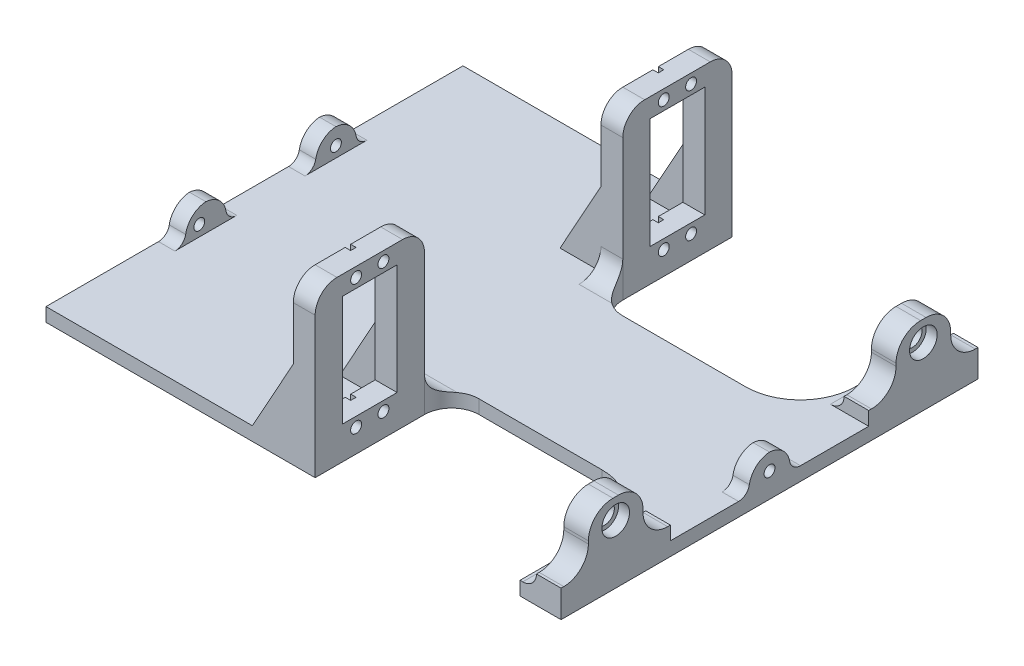
SolidWorks part; units mm, degrees
ref_plane "Front Plane" through (0, 0, 0) normal (0, 0, 1) x (1, 0, 0)
ref_plane "Top Plane" through (0, 0, 0) normal (0, 1, 0) x (1, 0, 0)
ref_plane "Right Plane" through (0, 0, 0) normal (1, 0, 0) x (0, 0, -1)
sketch "Sketch1" plane through (0, 0, 0) normal (0, 1, 0) x (1, 0, 0)
  line L1 (-183.5, 76.3) -> (183.5, 76.3)
  line L2 (-183.5, 76.3) -> (-183.5, -76.3)
  line L3 (-183.5, -76.3) -> (183.5, -76.3)
  line L4 (183.5, 76.3) -> (183.5, -76.3)
  line L5 (-183.5, 76.3) -> (183.5, -76.3) construction
  line L6 (-183.5, -76.3) -> (183.5, 76.3) construction
  point P0 (0, 0)
  dimension "D1" = 367
  dimension "D2" = 152.6
extrude "Boss-Extrude1" add sketch "Sketch1" along normal blind 5
sketch "Sketch2" plane through (0, 5, 0) normal (0, 1, 0) x (1, 0, 0)
  line L0 (173.5, -76.3) -> (173.5, -26.3)
  line L1 (-183.5, -76.3) -> (183.5, -76.3) construction
  line L2 (173.5, -26.3) -> (98.5, -26.3)
  line L3 (98.5, -26.3) -> (98.5, -76.3)
  line L4 (98.5, -76.3) -> (173.5, -76.3)
  line L5 (183.5, -76.3) -> (183.5, 76.3) construction
  dimension "D1" = 10
  dimension "D2" = 75
  dimension "D3" = 50
extrude "Cut-Extrude1" cut sketch "Sketch2" against normal through all
sketch "Sketch3" plane through (0, 5, 0) normal (0, 1, 0) x (1, 0, 0)
  line L0 (98.5, -36.3) -> (90.5, -36.3)
  line L1 (98.5, -26.3) -> (98.5, -76.3) construction
  line L2 (90.5, -36.3) -> (90.5, -76.3)
  line L3 (-183.5, -76.3) -> (98.5, -76.3) construction
  line L4 (90.5, -76.3) -> (98.5, -76.3)
  line L5 (98.5, -36.3) -> (98.5, -76.3)
  dimension "D1" = 8
  dimension "D2" = 40
extrude "Boss-Extrude2" add sketch "Sketch3" along normal blind 54.5
sketch "Sketch4" plane through (98.5, 0, 0) normal (1, 0, 0) x (0, 0, -1)
  line L0 (-76.3, 0) -> (-76.3, 59.5) construction
  line L1 (-66.3, 52.5) -> (-46.3, 52.5)
  line L2 (-66.3, 52.5) -> (-66.3, 12)
  line L3 (-66.3, 12) -> (-46.3, 12)
  line L4 (-46.3, 52.5) -> (-46.3, 12)
  line L5 (-66.3, 52.5) -> (-46.3, 12) construction
  line L6 (-66.3, 12) -> (-46.3, 52.5) construction
  line L12 (-76.3, 5) -> (76.3, 5) construction
  point P0 (-56.3, 32.25)
  dimension "D1" = 20
  dimension "D2" = 7
  dimension "D3" = 40.5
  dimension "D4" = 20
extrude "Cut-Extrude2" cut sketch "Sketch4" against normal blind 15
sketch "Sketch7" plane through (90.5, 0, 0) normal (-1, 0, 0) x (0, 0, 1)
  line L0 (46.3, 52.5) -> (66.3, 52.5) construction
  line L1 (55.3, 52.5) -> (57.3, 52.5)
  line L2 (55.3, 52.5) -> (55.3, 59.5)
  line L3 (55.3, 59.5) -> (57.3, 59.5)
  line L4 (57.3, 52.5) -> (57.3, 59.5)
  line L5 (55.3, 52.5) -> (57.3, 59.5) construction
  line L6 (55.3, 59.5) -> (57.3, 52.5) construction
  line L7 (36.3, 59.5) -> (76.3, 59.5) construction
  line L13 (-76.3, 5) -> (76.3, 5) construction
  line L14 (55.3, 12) -> (57.3, 12)
  line L17 (76.3, 59.5) -> (76.3, 5) construction
  line L18 (55.3, 12) -> (55.3, 5)
  line L19 (55.3, 5) -> (57.3, 5)
  line L20 (57.3, 12) -> (57.3, 5)
  line L21 (55.3, 12) -> (57.3, 5) construction
  line L22 (55.3, 5) -> (57.3, 12) construction
  point P4 (56.3, 56)
  point P9 (56.3, 8.5)
  point P13 (56.3, 8.5)
  dimension "D1" = 20
  dimension "D2" = 2
  dimension "D3" = 7
  dimension "D4" = 2
  dimension "D5" = 20
extrude "Cut-Extrude4" cut sketch "Sketch7" against normal blind 2
sketch "Sketch8" plane through (98.5, 0, 0) normal (1, 0, 0) x (0, 0, -1)
  line L0 (-46.3, 52.5) -> (-66.3, 52.5) construction
  line L1 (-76.3, 59.5) -> (-36.3, 59.5) construction
  line L2 (-66.3, 32.25) -> (-46.3, 32.25) construction
  line L3 (-66.3, 52.5) -> (-66.3, 12) construction
  line L4 (-46.3, 12) -> (-46.3, 52.5) construction
  circle A0 centre (-61.3, 56) radius 2
  circle A1 centre (-51.3, 56) radius 2
  circle A2 centre (-61.3, 8.5) radius 2
  circle A3 centre (-51.3, 8.5) radius 2
  point P6 (-56.3, 52.5)
  dimension "D1" = 4
  dimension "D2" = 4
  dimension "D3" = 5
  dimension "D4" = 5
  dimension "D5" = 3.5
  dimension "D6" = 3.5
extrude "Cut-Extrude5" cut sketch "Sketch8" against normal blind 15
fillet "Fillet1" radius 20 1 edges at (173.5, 2.5, 26.3)
fillet "Fillet3" radius 10 1 edges at (98.5, 2.5, 26.3)
fillet "Fillet9" radius 8 3 edges at (94.5, 5, 36.3) (94.5, 59.5, 36.3) (94.5, 59.5, 76.3)
sketch "Sketch13" plane through (0, 5, 0) normal (0, 1, 0) x (1, 0, 0)
  line L0 (183.5, 0) -> (-183.5, 0) construction
  line L1 (183.5, -76.3) -> (183.5, 76.3) construction
  line L2 (-183.5, 76.3) -> (-183.5, -76.3) construction
sketch "Sketch17" plane through (0, 5, 0) normal (0, 1, 0) x (1, 0, 0)
  line L0 (-183.5, -76.3) -> (90.5, -76.3) construction
  line L1 (-183.5, 76.3) -> (0, 76.3)
  line L2 (-183.5, 76.3) -> (-183.5, -76.3)
  line L3 (-183.5, -76.3) -> (0, -76.3)
  line L4 (0, 76.3) -> (0, -76.3)
  line L5 (-183.5, 76.3) -> (0, -76.3) construction
  line L6 (-183.5, -76.3) -> (0, 76.3) construction
  point P4 (-91.75, 0)
extrude "Cut-Extrude8" cut sketch "Sketch17" against normal through all both and the other way through all
sketch "Sketch18" plane through (0, 5, 0) normal (0, 1, 0) x (1, 0, 0)
  line L0 (20, 51.3) -> (20, -98.7)
  line L1 (20, -98.7) -> (100, -98.7)
  line L2 (100, -98.7) -> (100, -30)
  line L3 (100, -30) -> (163.5, -30)
  line L4 (163.5, -30) -> (163.5, 30)
  line L5 (163.5, 30) -> (100, 30)
  line L6 (100, 30) -> (100, 51.3)
  line L7 (100, 51.3) -> (20, 51.3)
  line L8 (183.5, 0) -> (-183.5, 0) construction
  line L9 (183.5, 76.3) -> (0, 76.3) construction
  line L10 (183.5, -76.3) -> (183.5, 76.3) construction
  line L11 (0, -76.3) -> (0, 76.3) construction
  dimension "D1" = 150
  dimension "D2" = 25
  dimension "D3" = 30
  dimension "D4" = 30
  dimension "D5" = 20
  dimension "D6" = 20
  dimension "D7" = 80
  dimension "D8" = 80
sketch "Sketch19" plane through (0, 5, 0) normal (0, 1, 0) x (1, 0, 0)
  line L1 (0, 31.3) -> (6, 31.3)
  line L2 (0, 31.3) -> (0, 16.3)
  line L3 (0, 16.3) -> (6, 16.3)
  line L4 (6, 31.3) -> (6, 16.3)
  line L5 (0, 31.3) -> (6, 16.3) construction
  line L6 (0, 16.3) -> (6, 31.3) construction
  line L9 (0, -31.3) -> (6, -31.3)
  line L10 (6, -16.3) -> (6, -31.3)
  line L11 (0, -16.3) -> (6, -16.3)
  line L13 (0, -16.3) -> (0, -31.3)
  line L15 (6, 7.5) -> (6, -7.5) [skipped]
  line L16 (0, -7.5) -> (6, -7.5) [skipped]
  line L17 (0, 7.5) -> (6, 7.5) [skipped]
  line L18 (0, -76.3) -> (90.5, -76.3) construction
  line L19 (183.5, 76.3) -> (0, 76.3) construction
  point P4 (3, 23.8)
  dimension "D1" = 6
  dimension "D2" = 15
  dimension "D4" = 45
  dimension "D5" = 45
  dimension "D3" = 3
extrude "Boss-Extrude4" add sketch "Sketch19" along normal blind 10
sketch "Sketch20" plane through (0, 0, 0) normal (-1, 0, 0) x (0, 0, 1)
  line L0 (-31.3, 5) -> (-31.3, 15) construction
  line L1 (16.3, 5) -> (-16.3, 5) construction
  circle A0 centre (-23.8, 9) radius 2
  circle A2 centre (26.2, 9) radius 2
  circle A3 centre (1.2, 9) radius 2 [skipped]
  dimension "D1" = 4
  dimension "D3" = 4
  dimension "D2" = 7.5
  dimension "D4" = 3
extrude "Cut-Extrude9" cut sketch "Sketch20" against normal blind 6
fillet "Fillet10" radius 8 4 edges at (3, 15, 16.3) (3, 15, 31.3) (3, 15, -16.3) (3, 15, -31.3)
fillet "Fillet11" radius 4 2 edges at (3, 5, 16.3) (3, 5, -16.3)
mirror "Mirror1" about plane through (0, 0, 0) normal (0, 0, 1) of "Cut-Extrude4", "Fillet3", "Fillet1", "Fillet9", "Boss-Extrude2", "Cut-Extrude5", "Cut-Extrude2", "Cut-Extrude1"
sketch "Sketch22" plane through (90.5, 0, 0) normal (-1, 0, 0) x (0, 0, 1)
  line L0 (-76.3, 51.5) -> (-76.3, 5) construction
  line L1 (-76.3, 32) -> (-68.3, 32)
  line L2 (-76.3, 32) -> (-76.3, 5)
  line L3 (-76.3, 5) -> (-68.3, 5)
  line L4 (-68.3, 32) -> (-68.3, 5)
  line L5 (-76.3, 32) -> (-68.3, 5) construction
  line L6 (-76.3, 5) -> (-68.3, 32) construction
  line L7 (-57.3, 5) -> (-76.3, 5) construction
  line L8 (-36.3, 51.5) -> (-36.3, 13) construction
  line L9 (-36.3, 32) -> (-44.3, 32)
  line L10 (-36.3, 32) -> (-36.3, 5)
  line L11 (-36.3, 5) -> (-44.3, 5)
  line L12 (-44.3, 32) -> (-44.3, 5)
  line L13 (-36.3, 32) -> (-44.3, 5) construction
  line L14 (-36.3, 5) -> (-44.3, 32) construction
  line L15 (-28.3, 5) -> (-55.3, 5) construction
  line L16 (36.3, 51.5) -> (36.3, 13) construction
  line L17 (36.3, 32) -> (44.3, 32)
  line L18 (36.3, 32) -> (36.3, 5)
  line L19 (36.3, 5) -> (44.3, 5)
  line L20 (44.3, 32) -> (44.3, 5)
  line L21 (36.3, 32) -> (44.3, 5) construction
  line L22 (36.3, 5) -> (44.3, 32) construction
  line L23 (28.3, 5) -> (55.3, 5) construction
  line L24 (76.3, 51.5) -> (76.3, 5) construction
  line L25 (76.3, 32) -> (68.3, 32)
  line L26 (76.3, 32) -> (76.3, 5)
  line L27 (76.3, 5) -> (68.3, 5)
  line L28 (68.3, 32) -> (68.3, 5)
  line L29 (76.3, 32) -> (68.3, 5) construction
  line L30 (76.3, 5) -> (68.3, 32) construction
  line L31 (57.3, 5) -> (76.3, 5) construction
  point P4 (-72.3, 18.5)
  point P13 (-40.3, 18.5)
  point P22 (40.3, 18.5)
  point P31 (72.3, 18.5)
  dimension "D1" = 8
  dimension "D2" = 8
  dimension "D3" = 27
  dimension "D4" = 27
  dimension "D5" = 27
  dimension "D6" = 8
  dimension "D7" = 8
  dimension "D8" = 27
extrude "Boss-Extrude6" add sketch "Sketch22" along normal blind 15
chamfer "Chamfer2" distance 15 angle 61 4 edges at (75.5, 32, 72.3) (75.5, 32, 40.3) (75.5, 32, -40.3) (75.5, 32, -72.3) first distance on face at (83, 32, 72.3) first distance on face at (83, 32, 40.3) first distance on face at (83, 32, -40.3) first distance on face at (83, 32, -72.3)
sketch "Sketch23" plane through (183.5, 0, 0) normal (1, 0, 0) x (0, 0, -1)
  line L1 (-76.3, 5) -> (76.3, 5)
  line L2 (-76.3, 5) -> (-76.3, 0)
  line L3 (-76.3, 0) -> (76.3, 0)
  line L4 (76.3, 5) -> (76.3, 0)
  line L5 (-76.3, 5) -> (76.3, 0) construction
  line L6 (-76.3, 0) -> (76.3, 5) construction
  point P4 (0, 2.5)
extrude "Boss-Extrude7" add sketch "Sketch23" along normal blind 5
sketch "Sketch24" plane through (0, 5, 0) normal (0, 1, 0) x (1, 0, 0)
  line L0 (107.5, 76.3) -> (107.5, -76.3) construction
  line L1 (75.5337, 76.3) -> (0, 76.3) construction
  line L2 (0, -76.3) -> (75.5337, -76.3) construction
  line L3 (0, -12.4678) -> (0, 12.4678) construction
  dimension "D1" = 107.5
ref_plane "Plane1" through (107.5, 0, 0) normal (1, 0, 0) x (0, 0, -1)
sketch "Sketch27" plane through (0, 5, 0) normal (0, 1, 0) x (1, 0, 0)
  line L1 (188.5, -76.3) -> (179.5, -76.3)
  line L2 (188.5, -76.3) -> (188.5, -36.3)
  line L3 (188.5, -36.3) -> (179.5, -36.3)
  line L4 (179.5, -76.3) -> (179.5, -36.3)
  line L5 (188.5, -76.3) -> (179.5, -36.3) construction
  line L6 (188.5, -36.3) -> (179.5, -76.3) construction
  point P4 (184, -56.3)
  dimension "D1" = 9
  dimension "D2" = 40
extrude "Boss-Extrude9" add sketch "Sketch27" along normal blind 5
sketch "Sketch28" plane through (0, 10, 0) normal (0, 1, 0) x (1, 0, 0)
  line L0 (188.5, -76.3) -> (188.5, -36.3) construction
  line L1 (188.5, -46.3) -> (179.5, -46.3)
  line L2 (188.5, -46.3) -> (188.5, -66.3)
  line L3 (188.5, -66.3) -> (179.5, -66.3)
  line L4 (179.5, -46.3) -> (179.5, -66.3)
  line L5 (188.5, -46.3) -> (179.5, -66.3) construction
  line L6 (188.5, -66.3) -> (179.5, -46.3) construction
  line L7 (179.5, -36.3) -> (179.5, -76.3) construction
  line L8 (188.5, -36.3) -> (179.5, -36.3) construction
  point P4 (184, -56.3)
  dimension "D1" = 20
  dimension "D2" = 20
extrude "Boss-Extrude10" add sketch "Sketch28" along normal blind 19
sketch "Sketch29" plane through (188.5, 0, 0) normal (1, 0, 0) x (0, 0, -1)
  line L0 (76.3, 5) -> (-76.3, 5) construction
  line L1 (-66.3, 29) -> (-66.3, 10) construction
  circle A0 centre (-56.3, 21.5) radius 5.055
  dimension "D2" = 10.11
  dimension "D1" = 16.5
  dimension "D3" = 10
extrude "Cut-Extrude11" cut sketch "Sketch29" against normal blind 4
sketch "Sketch30" plane through (184.5, 0, 0) normal (1, 0, 0) x (0, 0, -1)
  circle A0 centre (-56.3, 21.5) radius 3.5
  dimension "D1" = 7
extrude "Cut-Extrude12" cut sketch "Sketch30" against normal blind 10
fillet "Fillet13" radius 9 4 edges at (184, 10, 46.3) (184, 29, 46.3) (184, 29, 66.3) (184, 10, 66.3)
fillet "Fillet14" radius 5 1 edges at (179.5, 5, 56.3)
mirror "Mirror3" about plane through (0, 0, 0) normal (0, 0, 1) of "Cut-Extrude12", "Cut-Extrude11", "Fillet13", "Boss-Extrude10", "Fillet14", "Boss-Extrude9"
fillet "Fillet15" radius 4 2 edges at (3, 5, -31.3) (3, 5, 31.3)
sketch "Sketch35" plane through (0, 5, 0) normal (0, 1, 0) x (1, 0, 0)
  line L0 (188.5, 36.3) -> (188.5, -36.3) construction
  line L2 (182.5, 7.5) -> (188.5, 7.5)
  line L3 (182.5, 7.5) -> (182.5, -7.5)
  line L4 (182.5, -7.5) -> (188.5, -7.5)
  line L5 (188.5, 7.5) -> (188.5, -7.5)
  line L6 (182.5, 7.5) -> (188.5, -7.5) construction
  line L7 (182.5, -7.5) -> (188.5, 7.5) construction
  point P4 (185.5, 0)
  dimension "D1" = 0
  dimension "D2" = 6
  dimension "D3" = 15
extrude "Boss-Extrude11" add sketch "Sketch35" along normal blind 10
fillet "Fillet16" radius 8 2 edges at (185.5, 15, -7.5) (185.5, 15, 7.5)
fillet "Fillet17" radius 4 2 edges at (185.5, 5, -7.5) (185.5, 5, 7.5)
sketch "Sketch37" plane through (188.5, 0, 0) normal (1, 0, 0) x (0, 0, -1)
  line L0 (36.3, 5) -> (11.3322, 5) construction
  circle A0 centre (0, 9) radius 2
  dimension "D1" = 4
  dimension "D2" = 4
extrude "Cut-Extrude15" cut sketch "Sketch37" against normal blind 12
